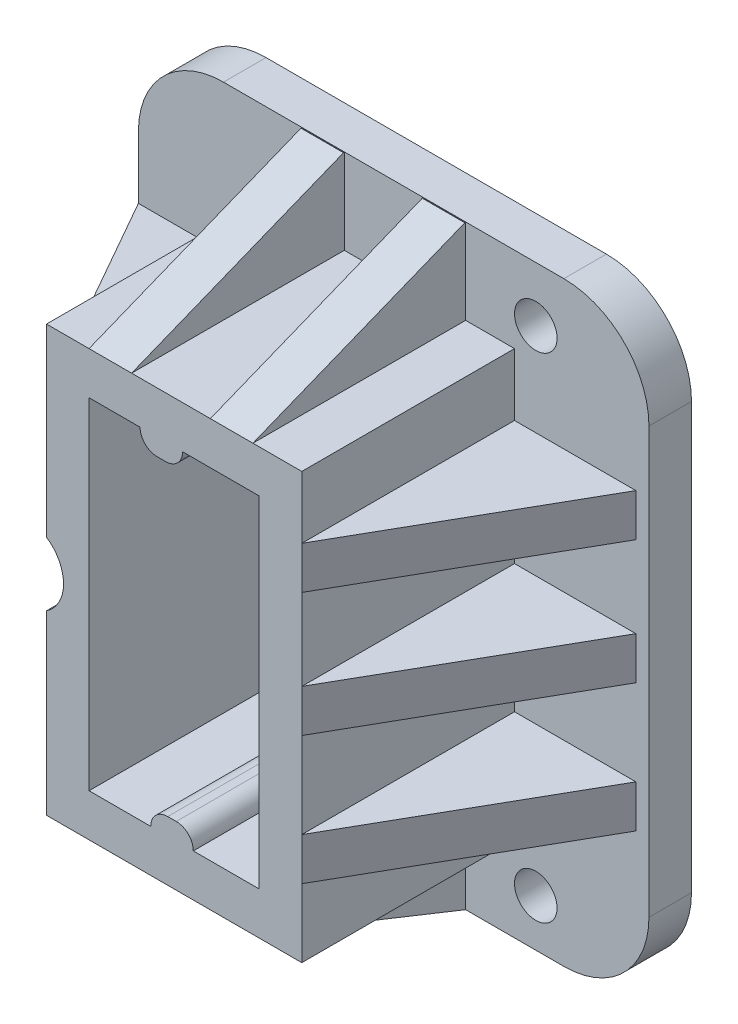
SolidWorks part; units mm, degrees
ref_plane "Front Plane" through (0, 0, 0) normal (0, 0, 1) x (1, 0, 0)
ref_plane "Top Plane" through (0, 0, 0) normal (0, 1, 0) x (1, 0, 0)
ref_plane "Right Plane" through (0, 0, 0) normal (1, 0, 0) x (0, 0, -1)
sketch "Sketch1" plane through (0, 0, 0) normal (0, 0, 1) x (1, 0, 0)
  line L1 (-33.6392, 54.6196) -> (6.3608, 54.6196)
  line L2 (-43.6392, 44.6196) -> (-43.6392, -5.3804)
  line L3 (-33.6392, -15.3804) -> (6.3608, -15.3804)
  line L4 (16.3608, 44.6196) -> (16.3608, -5.3804)
  circle A0 centre (3.0613, 48.1599) radius 2.5
  circle A2 centre (3.0613, -9.8401) radius 2.5
  circle A3 centre (-31.9387, 19.1599) radius 2.5
  arc A4 (6.3608, -15.3804) -> (16.3608, -5.3804) centre (6.3608, -5.3804) ccw
  arc A5 (-43.6392, -5.3804) -> (-33.6392, -15.3804) centre (-33.6392, -5.3804) ccw
  arc A6 (-33.6392, 54.6196) -> (-43.6392, 44.6196) centre (-33.6392, 44.6196) ccw
  arc A7 (6.3608, 54.6196) -> (16.3608, 44.6196) centre (6.3608, 44.6196) cw
  dimension "D3" = 5
  dimension "D4" = 10
  dimension "D1" = 60
  dimension "D2" = 70
extrude "Boss-Extrude1" add sketch "Sketch1" along normal blind 5
sketch "Sketch3" plane through (0, 0, 5) normal (0, 0, 1) x (1, 0, 0)
  line L0 (-33.6392, -15.3804) -> (6.3608, -15.3804) construction
  line L1 (-24.4387, 39.6004) -> (-4.4387, 39.6004)
  line L2 (-24.4387, 39.6004) -> (-24.4387, -0.3996)
  line L3 (-24.4387, -0.3996) -> (-4.4387, -0.3996)
  line L4 (-4.4387, 39.6004) -> (-4.4387, -0.3996)
  line L5 (-29.4387, 44.6004) -> (-24.4387, 44.6004)
  line L6 (-29.4387, 44.6004) -> (-29.4387, 37.282)
  line L7 (-29.4387, -5.3996) -> (-24.4387, -5.3996)
  line L8 (0.5613, 44.6004) -> (0.5613, 37.282)
  line L9 (0.5613, 37.282) -> (14.8252, 37.282)
  line L10 (-29.4387, 32.282) -> (-29.4387, 7.6373)
  line L11 (0.5613, 32.282) -> (14.8252, 32.282)
  line L12 (14.8252, 37.282) -> (14.8252, 32.282)
  line L13 (0.5613, 22.7197) -> (14.8252, 22.7197)
  line L14 (0.5613, 32.282) -> (0.5613, 22.7197)
  line L15 (0.5613, 17.7197) -> (14.8252, 17.7197)
  line L16 (14.8252, 22.7197) -> (14.8252, 17.7197)
  line L17 (0.5613, 7.6373) -> (14.8252, 7.6373)
  line L18 (0.5613, 17.7197) -> (0.5613, 7.6373)
  line L19 (0.5613, 2.6373) -> (14.8252, 2.6373)
  line L20 (14.8252, 7.6373) -> (14.8252, 2.6373)
  line L21 (-29.4387, 2.6373) -> (-43.7027, 2.6373)
  line L22 (-43.7027, 7.6373) -> (-43.7027, 2.6373)
  line L23 (-29.4387, 7.6373) -> (-43.7027, 7.6373)
  line L24 (-29.4387, 32.282) -> (-43.7027, 32.282)
  line L25 (-43.7027, 37.282) -> (-43.7027, 32.282)
  line L26 (-29.4387, 37.282) -> (-43.7027, 37.282)
  line L28 (-24.4387, -5.3996) -> (-24.4387, -15.3804)
  line L29 (-24.4387, -15.3804) -> (-19.4387, -15.3804)
  line L30 (-19.4387, -5.3996) -> (-19.4387, -15.3804)
  line L31 (0.5613, 2.6373) -> (0.5613, -5.3996)
  line L32 (-19.4387, -5.3996) -> (-10.1846, -5.3996)
  line L33 (-10.1846, -5.3996) -> (-10.1846, -15.3804)
  line L34 (-10.1846, -15.3804) -> (-5.1846, -15.3804)
  line L35 (-5.1846, -5.3996) -> (-5.1846, -15.3804)
  line L36 (-29.4387, 2.6373) -> (-29.4387, -5.3996)
  line L37 (-24.4387, -15.3804) -> (-19.4387, -15.3804)
  line L38 (-10.1846, -15.3804) -> (-5.1846, -15.3804)
  line L39 (-19.4387, 44.6004) -> (-10.1846, 44.6004)
  line L40 (-10.1846, 44.6004) -> (-10.1846, 54.5813)
  line L41 (-5.1846, 44.6004) -> (-5.1846, 54.5813)
  line L42 (-10.1846, 54.5813) -> (-5.1846, 54.5813)
  line L43 (-24.4387, 54.5813) -> (-19.4387, 54.5813)
  line L44 (-24.4387, 44.6004) -> (-24.4387, 54.5813)
  line L45 (-19.4387, 44.6004) -> (-19.4387, 54.5813)
  line L46 (-5.1846, 44.6004) -> (0.5613, 44.6004)
  line L47 (-5.1846, -5.3996) -> (0.5613, -5.3996)
  line M7 (-43.6392, 44.6196) -> (-43.6392, -5.3804)
  line M9 (-33.6392, -15.3804) -> (6.3608, -15.3804)
  dimension "D1" = 40
  dimension "D2" = 20
  dimension "D3" = 50
  dimension "D4" = 30
  dimension "D5" = 5
  dimension "D6" = 5
  dimension "D7" = 5
  dimension "D8" = 5
  dimension "D9" = 5
  dimension "D10" = 5
  dimension "D11" = 5
extrude "Boss-Extrude5" add sketch "Sketch3" along normal blind 25 contours L35 L47 L31 L19 L20 L17 L18 L15 L16 L13 L14 L11 L12 L9 L8 L46 L41 L42 L40 L39 L45 L43 L44 L5 L6 L26 L24 L10 L23 L21 L36 L7 L28 L30 L32 L33 L1 L4 L3 L2 M7 M9
sketch "Sketch5" plane through (0, 2.6373, 0) normal (0, -1, 0) x (1, 0, 0)
  line L0 (-43.6392, 5) -> (-29.4387, 30)
  line L1 (-29.4387, 30) -> (0.5613, 30)
  line L2 (0.5613, 30) -> (14.8252, 5)
extrude "Cut-Extrude2" cut sketch "Sketch5" along direction (0, 1, 0) on the side against the normal through all and the other way through all
sketch "Sketch7" plane through (-24.4387, 0, 0) normal (-1, 0, 0) x (0, 0, 1)
  line L0 (30, 44.6004) -> (5, 54.6196)
  line L1 (5, -15.3804) -> (30, -5.3996)
extrude "Cut-Extrude-Thin13" cut sketch "Sketch7" against normal through all thin
sketch "Sketch8" plane through (0, 39.6004, 0) normal (0, -1, 0) x (1, 0, 0)
  line L0 (-24.4387, 30) -> (-4.4387, 30) construction
  line L1 (-18.4387, 30) -> (-13.4387, 30)
  line L2 (-18.4387, 30) -> (-18.4387, 5)
  line L3 (-18.4387, 5) -> (-13.4387, 5)
  line L4 (-13.4387, 30) -> (-13.4387, 5)
  line L5 (-24.4387, 5) -> (-4.4387, 5) construction
  dimension "D1" = 5
extrude "Boss-Extrude6" add sketch "Sketch8" along normal blind 2
fillet "Fillet3" radius 2 2 edges at (-18.4387, 37.6004, 17.5) (-13.4387, 37.6004, 17.5)
sketch "Sketch9" plane through (0, -0.3996, 0) normal (0, 1, 0) x (1, 0, 0)
  line L0 (-24.4387, -5) -> (-4.4387, -5) construction
  line L1 (-17.1905, -5) -> (-12.1905, -5)
  line L2 (-17.1905, -5) -> (-17.1905, -30)
  line L3 (-17.1905, -30) -> (-12.1905, -30)
  line L4 (-12.1905, -5) -> (-12.1905, -30)
  line L5 (-24.4387, -30) -> (-4.4387, -30) construction
  dimension "D1" = 5
extrude "Boss-Extrude7" add sketch "Sketch9" along normal blind 2
fillet "Fillet4" radius 2 2 edges at (-12.1905, 1.6004, 17.5) (-17.1905, 1.6004, 17.5)
sketch "Sketch11" plane through (0, 0, 30) normal (0, 0, 1) x (1, 0, 0)
  circle A0 centre (-31.9387, 19.1599) radius 4.5
extrude "Cut-Extrude4" cut sketch "Sketch11" along a picked direction on the side against the normal blind 25
